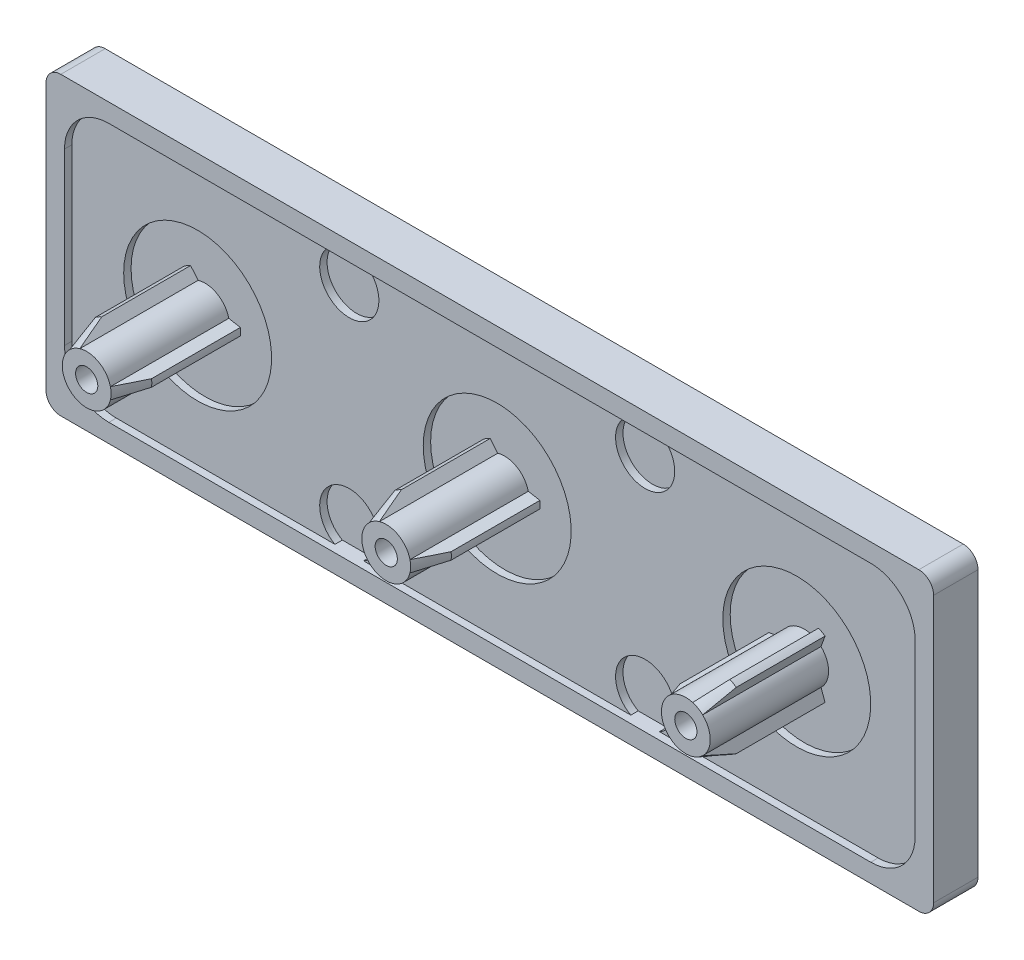
SolidWorks part; units mm, degrees
ref_plane "Front Plane" through (0, 0, 0) normal (0, 0, 1) x (1, 0, 0)
ref_plane "Top Plane" through (0, 0, 0) normal (0, 1, 0) x (1, 0, 0)
ref_plane "Right Plane" through (0, 0, 0) normal (1, 0, 0) x (0, 0, -1)
ref_plane "Plane1" through (0, 0, 0) normal (0, 0, 1) x (1, 0, 0)
sketch "Sketch1" plane through (0, 0, 0) normal (0, 0, 1) x (1, 0, 0)
  line L0 (-29, -10) -> (29, -10)
  line L1 (30, -9) -> (30, 9)
  line L2 (29, 10) -> (-29, 10)
  line L3 (-30, 9) -> (-30, -9)
  arc A0 (-30, -9) -> (-29, -10) centre (-29, -9) ccw
  arc A1 (29, -10) -> (30, -9) centre (29, -9) ccw
  arc A2 (30, 9) -> (29, 10) centre (29, 9) ccw
  arc A3 (-29, 10) -> (-30, 9) centre (-29, 9) ccw
extrude "Boss-Extrude1" add sketch "Sketch1" against normal blind 3
ref_plane "Plane2" through (0, 0, 0) normal (0, 0, 1) x (1, 0, 0)
sketch "Sketch2" plane through (0, 0, 0) normal (0, 0, 1) x (1, 0, 0)
  line L0 (-25.75, -8.75) -> (25.75, -8.75)
  line L1 (28.75, -5.75) -> (28.75, 5.75)
  line L2 (25.75, 8.75) -> (-25.75, 8.75)
  line L3 (-28.75, 5.75) -> (-28.75, -5.75)
  arc A0 (-28.75, -5.75) -> (-25.75, -8.75) centre (-25.75, -5.75) ccw
  arc A1 (25.75, -8.75) -> (28.75, -5.75) centre (25.75, -5.75) ccw
  arc A2 (28.75, 5.75) -> (25.75, 8.75) centre (25.75, 5.75) ccw
  arc A3 (-25.75, 8.75) -> (-28.75, 5.75) centre (-25.75, 5.75) ccw
extrude "Cut-Extrude1" cut sketch "Sketch2" against normal blind 0.5
ref_plane "Plane3" through (0, 0, 0) normal (0, 1, 0) x (1, 0, 0)
sketch "Sketch3" plane through (0, 0, 0) normal (0, 1, 0) x (1, 0, 0)
  line L0 (-20.25, 1) -> (-15.25, 1)
  line L1 (-15.25, 1) -> (-15.25, 0.5)
  line L2 (-15.25, 0.5) -> (-20.25, 0.5)
  line L3 (-20.25, 0.5) -> (-20.25, 1)
  line L4 (-20.25, 0.5) -> (-20.25, 1) construction
revolve "Cut-Revolve1" cut sketch "Sketch3" angle 360 about L4 reverse direction yes
ref_plane "Plane4" through (0, 0, 0) normal (0, 1, 0) x (1, 0, 0)
sketch "Sketch4" plane through (0, 0, 0) normal (0, 1, 0) x (1, 0, 0)
  line L0 (0, 1) -> (5, 1)
  line L1 (5, 1) -> (5, 0.5)
  line L2 (5, 0.5) -> (0, 0.5)
  line L3 (0, 0.5) -> (0, 1)
  line L4 (0, 0.5) -> (0, 1) construction
revolve "Cut-Revolve2" cut sketch "Sketch4" angle 360 about L4 reverse direction yes
ref_plane "Plane5" through (0, 0, 0) normal (0, 1, 0) x (1, 0, 0)
sketch "Sketch5" plane through (0, 0, 0) normal (0, 1, 0) x (1, 0, 0)
  line L0 (20.25, 1) -> (25.25, 1)
  line L1 (25.25, 1) -> (25.25, 0.5)
  line L2 (25.25, 0.5) -> (20.25, 0.5)
  line L3 (20.25, 0.5) -> (20.25, 1)
  line L4 (20.25, 0.5) -> (20.25, 1) construction
revolve "Cut-Revolve3" cut sketch "Sketch5" angle 360 about L4 reverse direction yes
ref_plane "Plane6" through (0, 0, -0.5) normal (0, 0, 1) x (1, 0, 0)
sketch "Sketch6" plane through (0, 0, -0.5) normal (0, 0, 1) x (1, 0, 0)
  line L0 (-9.0318, 8.75) -> (-10.9682, 8.75)
  arc A0 (-10.9682, 8.75) -> (-9.0318, 8.75) centre (-10, 7) ccw
extrude "Cut-Extrude2" cut sketch "Sketch6" against normal blind 0.5
ref_plane "Plane7" through (0, 0, -0.5) normal (0, 0, 1) x (1, 0, 0)
sketch "Sketch7" plane through (0, 0, -0.5) normal (0, 0, 1) x (1, 0, 0)
  line L0 (10.9682, 8.75) -> (9.0318, 8.75)
  arc A0 (9.0318, 8.75) -> (10.9682, 8.75) centre (10, 7) ccw
extrude "Cut-Extrude3" cut sketch "Sketch7" against normal blind 0.5
ref_plane "Plane8" through (0, 0, -0.5) normal (0, 0, 1) x (1, 0, 0)
sketch "Sketch8" plane through (0, 0, -0.5) normal (0, 0, 1) x (1, 0, 0)
  line L0 (-10.9682, -8.75) -> (-9.0318, -8.75)
  arc A0 (-9.0318, -8.75) -> (-10.9682, -8.75) centre (-10, -7) ccw
extrude "Cut-Extrude4" cut sketch "Sketch8" against normal blind 0.5
ref_plane "Plane9" through (0, 0, -0.5) normal (0, 0, 1) x (1, 0, 0)
sketch "Sketch9" plane through (0, 0, -0.5) normal (0, 0, 1) x (1, 0, 0)
  line L0 (9.0318, -8.75) -> (10.9682, -8.75)
  arc A0 (10.9682, -8.75) -> (9.0318, -8.75) centre (10, -7) ccw
extrude "Cut-Extrude5" cut sketch "Sketch9" against normal blind 0.5
ref_plane "Plane10" through (0, 0, -1) normal (0, 0, 1) x (1, 0, 0)
sketch "Sketch10" plane through (0, 0, -1) normal (0, 0, 1) x (1, 0, 0)
  line L0 (-1.1394, -1.1935) -> (-1.41, -1.9422)
  line L1 (-0.977, -2.1922) -> (-0.4639, -1.5835)
  line L2 (1.6032, -0.39) -> (2.3869, -0.25)
  line L3 (2.3869, 0.25) -> (1.6032, 0.39)
  line L4 (-0.4639, 1.5835) -> (-0.977, 2.1922)
  line L5 (-1.41, 1.9422) -> (-1.1394, 1.1935)
  arc A0 (-1.1394, 1.1935) -> (-1.1394, -1.1935) centre (0, 0) ccw
  arc A1 (-1.41, -1.9422) -> (-0.977, -2.1922) centre (0, 0) ccw
  arc A2 (-0.4639, -1.5835) -> (1.6032, -0.39) centre (0, 0) ccw
  arc A3 (2.3869, -0.25) -> (2.3869, 0.25) centre (0, 0) ccw
  arc A4 (1.6032, 0.39) -> (-0.4639, 1.5835) centre (0, 0) ccw
  arc A5 (-0.977, 2.1922) -> (-1.41, 1.9422) centre (0, 0) ccw
extrude "Boss-Extrude2" add sketch "Sketch10" along normal blind 8
ref_plane "Plane11" through (0, 0, -1) normal (0, 0, 1) x (1, 0, 0)
sketch "Sketch11" plane through (0, 0, -1) normal (0, 0, 1) x (1, 0, 0)
  line L0 (-21.3894, -1.1935) -> (-21.66, -1.9422)
  line L1 (-21.227, -2.1922) -> (-20.7139, -1.5835)
  line L2 (-18.6468, -0.39) -> (-17.8631, -0.25)
  line L3 (-17.8631, 0.25) -> (-18.6468, 0.39)
  line L4 (-20.7139, 1.5835) -> (-21.227, 2.1922)
  line L5 (-21.66, 1.9422) -> (-21.3894, 1.1935)
  arc A0 (-21.3894, 1.1935) -> (-21.3894, -1.1935) centre (-20.25, 0) ccw
  arc A1 (-21.66, -1.9422) -> (-21.227, -2.1922) centre (-20.25, 0) ccw
  arc A2 (-20.7139, -1.5835) -> (-18.6468, -0.39) centre (-20.25, 0) ccw
  arc A3 (-17.8631, -0.25) -> (-17.8631, 0.25) centre (-20.25, 0) ccw
  arc A4 (-18.6468, 0.39) -> (-20.7139, 1.5835) centre (-20.25, 0) ccw
  arc A5 (-21.227, 2.1922) -> (-21.66, 1.9422) centre (-20.25, 0) ccw
extrude "Boss-Extrude3" add sketch "Sketch11" along normal blind 8
ref_plane "Plane12" through (0, 0, -1) normal (0, 0, 1) x (1, 0, 0)
sketch "Sketch12" plane through (0, 0, -1) normal (0, 0, 1) x (1, 0, 0)
  line L0 (17.8631, -0.25) -> (18.6468, -0.39)
  line L1 (20.7139, -1.5835) -> (21.227, -2.1922)
  line L2 (21.66, -1.9422) -> (21.3894, -1.1935)
  line L3 (21.3894, 1.1935) -> (21.66, 1.9422)
  line L4 (21.227, 2.1922) -> (20.7139, 1.5835)
  line L5 (18.6468, 0.39) -> (17.8631, 0.25)
  arc A0 (17.8631, 0.25) -> (17.8631, -0.25) centre (20.25, 0) ccw
  arc A1 (18.6468, -0.39) -> (20.7139, -1.5835) centre (20.25, 0) ccw
  arc A2 (21.227, -2.1922) -> (21.66, -1.9422) centre (20.25, 0) ccw
  arc A3 (21.3894, -1.1935) -> (21.3894, 1.1935) centre (20.25, 0) ccw
  arc A4 (21.66, 1.9422) -> (21.227, 2.1922) centre (20.25, 0) ccw
  arc A5 (20.7139, 1.5835) -> (18.6468, 0.39) centre (20.25, 0) ccw
extrude "Boss-Extrude4" add sketch "Sketch12" along normal blind 8
ref_plane "Plane13" through (0, 0, 0) normal (0, 1, 0) x (1, 0, 0)
sketch "Sketch13" plane through (0, 0, 0) normal (0, 1, 0) x (1, 0, 0)
  line L0 (-18.7125, -7.3) -> (-17.55, -7.3)
  line L1 (-17.55, -7.3) -> (-17.55, -4.2)
  line L2 (-17.55, -4.2) -> (-18.7125, -7.3)
  line L3 (-20.25, -50) -> (-20.25, 50) construction
revolve "Cut-Revolve4" cut sketch "Sketch13" angle 360 about L3 reverse direction yes
ref_plane "Plane14" through (0, 0, 0) normal (0, 1, 0) x (1, 0, 0)
sketch "Sketch14" plane through (0, 0, 0) normal (0, 1, 0) x (1, 0, 0)
  line L0 (1.5375, -7.3) -> (2.7, -7.3)
  line L1 (2.7, -7.3) -> (2.7, -4.2)
  line L2 (2.7, -4.2) -> (1.5375, -7.3)
  line L3 (0, -50) -> (0, 50) construction
revolve "Cut-Revolve5" cut sketch "Sketch14" angle 360 about L3 reverse direction yes
ref_plane "Plane15" through (0, 0, 0) normal (0, 1, 0) x (1, 0, 0)
sketch "Sketch15" plane through (0, 0, 0) normal (0, 1, 0) x (1, 0, 0)
  line L0 (21.7875, -7.3) -> (22.95, -7.3)
  line L1 (22.95, -7.3) -> (22.95, -4.2)
  line L2 (22.95, -4.2) -> (21.7875, -7.3)
  line L3 (20.25, -50) -> (20.25, 50) construction
revolve "Cut-Revolve6" cut sketch "Sketch15" angle 360 about L3 reverse direction yes
ref_plane "Plane16" through (0, 0, 0) normal (0, 1, 0) x (1, 0, 0)
sketch "Sketch16" plane through (0, 0, 0) normal (0, 1, 0) x (1, 0, 0)
  line L0 (-20.25, 1) -> (-19.5, 1)
  line L1 (-19.5, 1) -> (-19.5, -7)
  line L2 (-19.5, -7) -> (-20.25, -7)
  line L3 (-20.25, -7) -> (-20.25, 1)
  line L4 (-20.25, -7) -> (-20.25, 1) construction
revolve "Cut-Revolve7" cut sketch "Sketch16" angle 360 about L4 reverse direction yes
ref_plane "Plane17" through (0, 0, 0) normal (0, 1, 0) x (1, 0, 0)
sketch "Sketch17" plane through (0, 0, 0) normal (0, 1, 0) x (1, 0, 0)
  line L0 (0, 1) -> (0.75, 1)
  line L1 (0.75, 1) -> (0.75, -7)
  line L2 (0.75, -7) -> (0, -7)
  line L3 (0, -7) -> (0, 1)
  line L4 (0, -7) -> (0, 1) construction
revolve "Cut-Revolve8" cut sketch "Sketch17" angle 360 about L4 reverse direction yes
ref_plane "Plane18" through (0, 0, 0) normal (0, 1, 0) x (1, 0, 0)
sketch "Sketch18" plane through (0, 0, 0) normal (0, 1, 0) x (1, 0, 0)
  line L0 (20.25, 1) -> (21, 1)
  line L1 (21, 1) -> (21, -7)
  line L2 (21, -7) -> (20.25, -7)
  line L3 (20.25, -7) -> (20.25, 1)
  line L4 (20.25, -7) -> (20.25, 1) construction
revolve "Cut-Revolve9" cut sketch "Sketch18" angle 360 about L4 reverse direction yes
